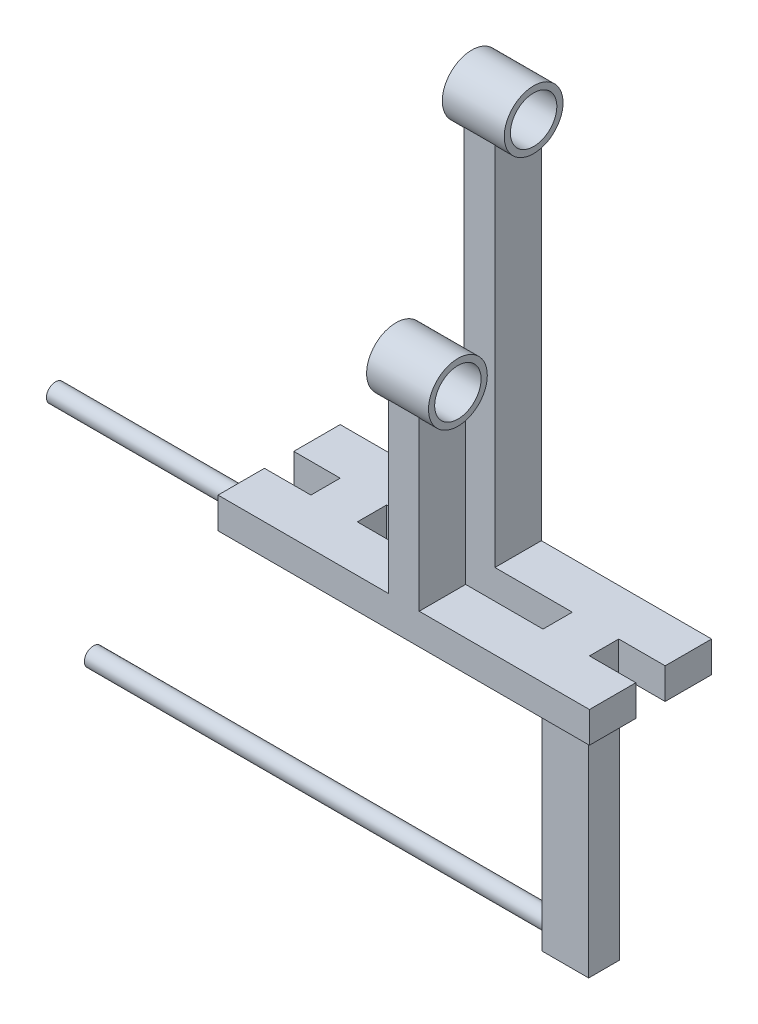
SolidWorks part; units mm, degrees
ref_plane "Front Plane" through (0, 0, 0) normal (0, 0, 1) x (1, 0, 0)
ref_plane "Top Plane" through (0, 0, 0) normal (0, 1, 0) x (1, 0, 0)
ref_plane "Right Plane" through (0, 0, 0) normal (1, 0, 0) x (0, 0, -1)
sketch "Sketch2" plane through (0, 0, 0) normal (0, 1, 0) x (1, 0, 0)
  line L33 (60, -15) -> (-60, -15)
  line L34 (-60, -15) -> (-60, 0)
  line L46 (-60, 0) -> (-45, 0)
  line L47 (-45, 0) -> (-45, 9.4666)
  line L48 (-45, 9.4666) -> (-60, 9.4666)
  line L49 (-60, 9.4666) -> (-60, 24.4666)
  line L50 (-60, 24.4666) -> (60, 24.4666)
  line L51 (60, 24.4666) -> (60, 9.4666)
  line L52 (60, 9.4666) -> (45, 9.4666)
  line L53 (45, 9.4666) -> (45, 0)
  line L54 (45, 0) -> (60, 0)
  line L55 (60, 0) -> (60, -15)
  line L57 (-30, 0) -> (30, 0)
  line L58 (-30, 0) -> (-30, 9.4666)
  line L59 (-30, 9.4666) -> (30, 9.4666)
  line L60 (30, 0) -> (30, 9.4666)
  point P21 (0, 0)
  dimension "D1" = 120
  dimension "D2" = 39.4666
  dimension "D3" = 15
  dimension "D4" = 60
  dimension "D5" = 15
  dimension "D6" = 15
extrude "Boss-Extrude2" add sketch "Sketch2" along normal blind 10
sketch "Sketch3" plane through (0, 10, 0) normal (0, 1, 0) x (1, 0, 0)
  line L0 (-30, 0) -> (30, 0) construction
  line L1 (-5, 0) -> (5, 0)
  line L2 (-5, 0) -> (-5, -15)
  line L3 (-5, -15) -> (5, -15)
  line L4 (5, 0) -> (5, -15)
  line L5 (-60, -15) -> (60, -15) construction
  line L6 (60, 24.4666) -> (-60, 24.4666) construction
  line L7 (-5, 24.4666) -> (5, 24.4666)
  line L8 (-5, 24.4666) -> (-5, 9.4666)
  line L9 (-5, 9.4666) -> (5, 9.4666)
  line L10 (5, 24.4666) -> (5, 9.4666)
  line L11 (30, 9.4666) -> (-30, 9.4666) construction
  dimension "D1" = 5
  dimension "D2" = 10
extrude "Boss-Extrude3" add sketch "Sketch3" along normal blind 60
sketch "Sketch4" plane through (0, 70, 0) normal (0, 1, 0) x (1, 0, 0)
  line L4 (-5, 24.4666) -> (-5, 9.4666)
  line L5 (-5, 9.4666) -> (5, 9.4666)
  line L6 (5, 9.4666) -> (5, 24.4666)
  line L7 (5, 24.4666) -> (-5, 24.4666)
  line L8 (-5, 24.4666) -> (-5, 9.4666)
  line L9 (-5, 9.4666) -> (5, 9.4666)
  line L10 (5, 9.4666) -> (5, 24.4666)
  line L11 (5, 24.4666) -> (-5, 24.4666)
  dimension "D1" = 0
extrude "Boss-Extrude4" add sketch "Sketch4" along normal blind 64.0503
sketch "Sketch6" plane through (0, 0, 0) normal (1, 0, 0) x (0, 0, -1)
  line L0 (-15, 70) -> (0, 70) construction
  line L1 (9.4666, 134.0503) -> (24.4666, 134.0503) construction
  line L2 (0, 70) -> (0, 10) construction
  line L3 (24.4666, 134.0503) -> (24.4666, 10) construction
  circle A0 centre (-7.5, 70) radius 7.5
  circle A1 centre (16.9666, 134.0503) radius 7.5
  dimension "D1" = 15
  dimension "D2" = 7.5
  dimension "D3" = 7.5
extrude "Extrude-Thin1" add sketch "Sketch6" along normal mid plane 20 thin thin type one direction wall 2
sketch "Sketch7" plane through (5, 0, 0) normal (1, 0, 0) x (0, 0, -1)
  line L1 (0, 70) -> (-15, 70)
  line L2 (0, 70) -> (-15, 70)
  line L3 (24.4666, 134.0503) -> (9.4666, 134.0503)
  line L4 (24.4666, 134.0503) -> (9.4666, 134.0503)
  arc A1 (-15, 70) -> (0, 70) centre (-7.5, 70) ccw
  arc A2 (-15, 70) -> (0, 70) centre (-7.5, 70) ccw
  arc A3 (9.4666, 134.0503) -> (24.4666, 134.0503) centre (16.9666, 134.0503) ccw
  arc A4 (9.4666, 134.0503) -> (24.4666, 134.0503) centre (16.9666, 134.0503) ccw
  dimension "D1" = 0
  dimension "D2" = 0
extrude "Cut-Extrude1" cut sketch "Sketch7" against normal through all both and the other way through all
sketch "Sketch8" plane through (0, 0, 0) normal (0, -1, 0) x (1, 0, 0)
  line L0 (30, 0) -> (30, -9.4666) construction
  line L1 (30, -9.75) -> (45, -9.75)
  line L2 (30, -9.75) -> (30, 0.25)
  line L3 (30, 0.25) -> (45, 0.25)
  line L4 (45, -9.75) -> (45, 0.25)
  line L5 (45, 0) -> (45, -9.4666) construction
  line L6 (-60, 15) -> (60, 15) construction
  dimension "D1" = 10
  dimension "D2" = 14.75
extrude "Boss-Extrude5" add sketch "Sketch8" along normal blind 80
sketch "Sketch9" plane through (30, 0, 0) normal (-1, 0, 0) x (0, 0, 1)
  line L0 (0.25, -80) -> (0.25, 0) construction
  line L1 (0.25, -80) -> (-9.75, -80) construction
  circle A0 centre (-4.75, -75) radius 2.95
  dimension "D1" = 5.9
  dimension "D2" = 5
  dimension "D3" = 5
extrude "Boss-Extrude6" add sketch "Sketch9" along normal blind 150
sketch "Sketch10" plane through (-60, 0, 0) normal (-1, 0, 0) x (0, 0, 1)
  line L0 (0, 10) -> (15, 10) construction
  line L1 (15, 10) -> (15, 0) construction
  circle A0 centre (7.5, 5) radius 2.95
  dimension "D1" = 5.9
  dimension "D2" = 5
  dimension "D3" = 7.5
extrude "Boss-Extrude7" add sketch "Sketch10" along normal blind 60
ref_plane "Plane1" through (0, 11.4078, 29.8742) normal (0, 0.3567, 0.9342) x (-1, 0, 0)
ref_plane "MatingPlane" through (0, 23.644, 61.9174) normal (0, 0.3567, 0.9342) x (-1, 0, 0)
